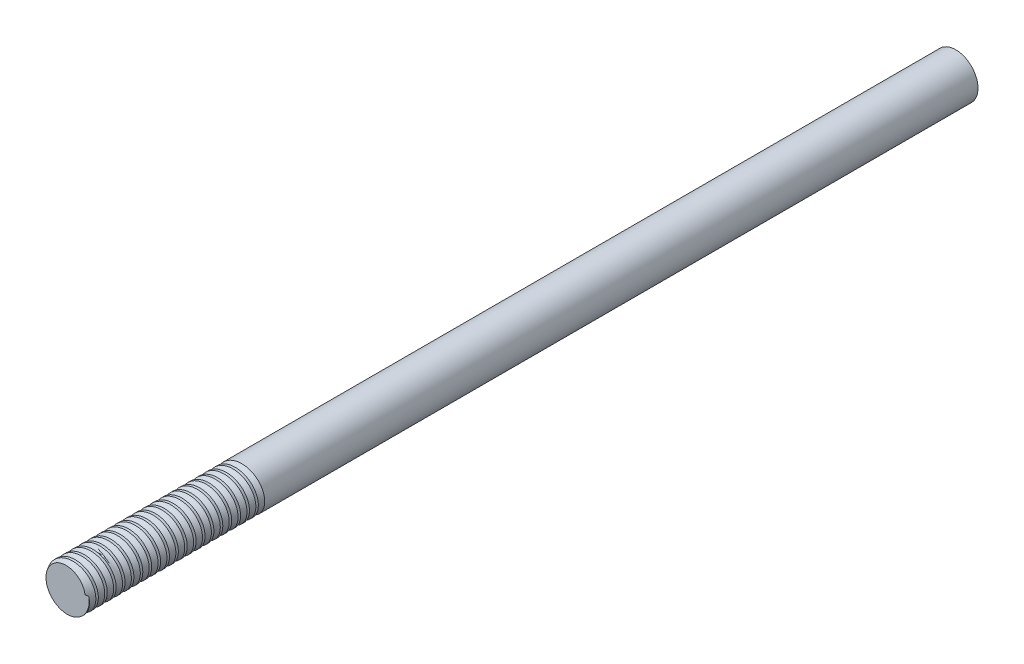
SolidWorks part; units mm, degrees
ref_plane "Front Plane" through (0, 0, 0) normal (0, 0, 1) x (1, 0, 0)
ref_plane "Top Plane" through (0, 0, 0) normal (0, 1, 0) x (1, 0, 0)
ref_plane "Right Plane" through (0, 0, 0) normal (1, 0, 0) x (0, 0, -1)
sketch "Sketch2" plane through (0, 0, 0) normal (0, 0, 1) x (1, 0, 0)
  circle A0 centre (0, 0) radius 3.175
  dimension "D1" = 6.35
extrude "Boss-Extrude1" add sketch "Sketch2" along normal blind 127
sketch "Sketch3" plane through (0, 0, 127) normal (0, 0, 1) x (1, 0, 0)
  circle A0 centre (0, 0) radius 3.175
  circle A1 centre (0, 0) radius 3.175 construction
curve "Helix/Spiral1" pitch 1.27 height 25.4 radius 3.175 centre (0, 0, 127) axis (0, 0, -1) start towards (1, 0, 0)
sketch "Sketch4" plane through (0, 0, 0) normal (1, 0, 0) x (0, 0, -1)
  line L0 (-127.9144, -2.6471) -> (-127.9144, -3.7029)
  line L1 (-127.9144, -2.6471) -> (-127, -3.175)
  line L2 (-127, -3.175) -> (-127.9144, -3.7029)
  circle A0 centre (-127.6096, -3.175) radius 0.6096 construction
  dimension "D1" = 1.2192
sweep "Cut-Sweep8" cut profiles "Sketch4" path "Helix/Spiral1"
